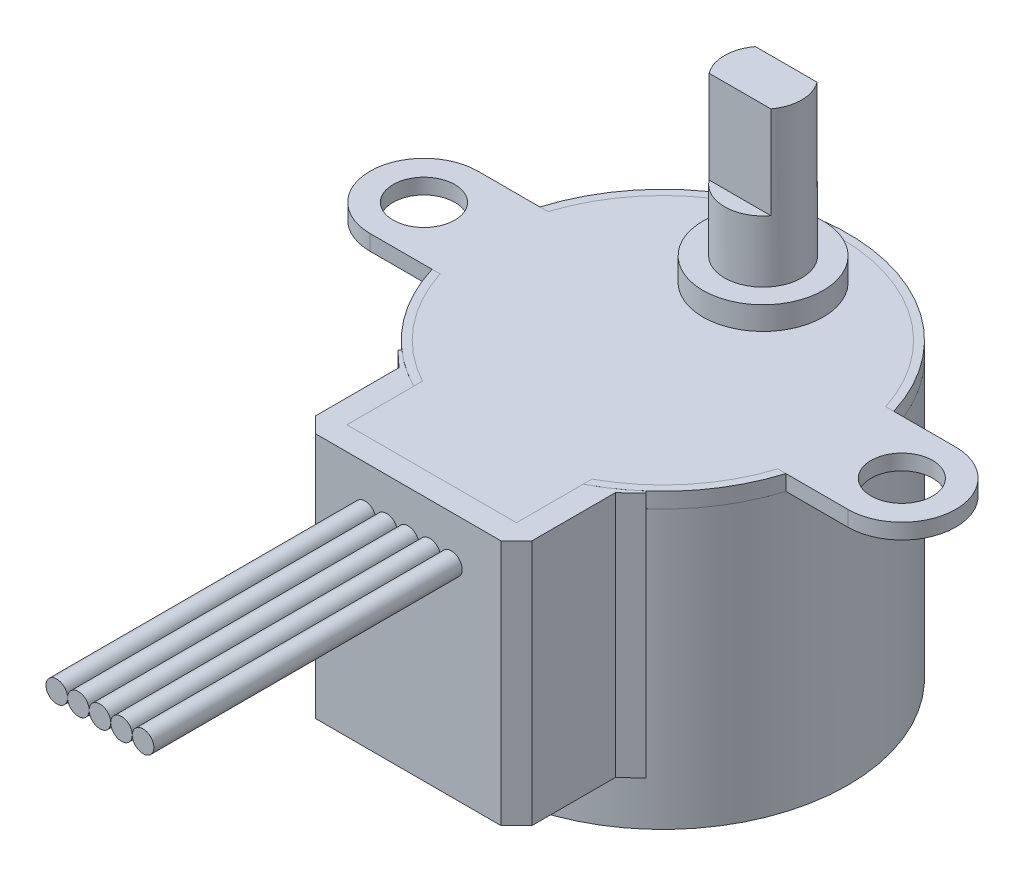
SolidWorks part; units mm, degrees
ref_plane "Front Plane" through (0, 0, 0) normal (0, 0, 1) x (1, 0, 0)
ref_plane "Top Plane" through (0, 0, 0) normal (0, 1, 0) x (1, 0, 0)
ref_plane "Right Plane" through (0, 0, 0) normal (1, 0, 0) x (0, 0, -1)
sketch "Sketch1" plane through (0, 0, 0) normal (0, 1, 0) x (1, 0, 0)
  circle A0 centre (0, 0) radius 12
  dimension "D1" = 24
extrude "Boss-Extrude1" add sketch "Sketch1" along normal blind 18
sketch "Sketch2" plane through (0, 18, 0) normal (0, 1, 0) x (1, 0, 0)
  line L0 (0, 16.9887) -> (0, 11.5) construction
  line L1 (10.9545, 3.5) -> (15.5, 3.5)
  line L2 (15.5, -3.5) -> (10.9545, -3.5)
  line L3 (-15.5, -3.5) -> (-10.9545, -3.5)
  line L4 (-10.9545, 3.5) -> (-15.5, 3.5)
  line L5 (-5.5, -10.0995) -> (-5.5, -15)
  line L6 (-5.5, -15) -> (5.5, -15)
  line L7 (5.5, -10.0995) -> (5.5, -15)
  line L8 (0, -11.5) -> (0, -20.5487) construction
  arc A0 (10.9545, 3.5) -> (-10.9545, 3.5) centre (0, 0) ccw
  circle A1 centre (15.5, 0) radius 2
  arc A2 (15.5, -3.5) -> (15.5, 3.5) centre (15.5, 0) ccw
  arc A3 (-15.5, -3.5) -> (-15.5, 3.5) centre (-15.5, 0) cw
  circle A4 centre (-15.5, 0) radius 2
  arc A5 (-10.9545, -3.5) -> (-5.5, -10.0995) centre (0, 0) ccw
  arc A6 (5.5, -10.0995) -> (10.9545, -3.5) centre (0, 0) ccw
  point P20 (0, -15)
  dimension "D1" = 23
  dimension "D3" = 4
  dimension "D2" = 15.5
  dimension "D4" = 3.5
  dimension "D5" = 7
  dimension "D6" = 15
  dimension "D7" = 5.5
extrude "Boss-Extrude2" add sketch "Sketch2" along normal blind 1 separate body
sketch "Sketch3" plane through (0, 18, 0) normal (0, 1, 0) x (1, 0, 0)
  line L0 (-11.4782, 3.5) -> (-10.9545, 3.5)
  line L3 (11.4782, -3.5) -> (10.9545, -3.5)
  line L5 (10.9545, 3.5) -> (11.4782, 3.5)
  line L6 (-10.9545, -3.5) -> (-11.4782, -3.5)
  line L7 (-5.5, -10.0995) -> (-5.5, -10.6654)
  line L8 (-5.5, -10.0995) -> (-5.5, -15) construction
  line L9 (5.5, -10.0995) -> (5.5, -10.6654)
  line L10 (5.5, -15) -> (5.5, -10.0995) construction
  arc A0 (-10.9545, -3.5) -> (-5.5, -10.0995) centre (0, 0) ccw
  circle A1 centre (0, 0) radius 12
  arc A2 (-11.4782, -3.5) -> (-5.5, -10.6654) centre (0, 0) ccw
  arc A3 (10.9545, 3.5) -> (-10.9545, 3.5) centre (0, 0) ccw
  arc A4 (11.4782, 3.5) -> (-11.4782, 3.5) centre (0, 0) ccw
  arc A5 (5.5, -10.0995) -> (10.9545, -3.5) centre (0, 0) ccw
  arc A6 (5.5, -10.6654) -> (11.4782, -3.5) centre (0, 0) ccw
  dimension "D1" = 0
extrude "Boss-Extrude3" add sketch "Sketch3" along normal blind 1 separate body
sketch "Sketch4" plane through (0, 19, 0) normal (0, 1, 0) x (1, 0, 0)
  line L0 (5.5, -15) -> (5.5, -10.0995) construction
  line L1 (-5.5, -15) -> (5.5, -15) construction
  line L2 (-5.5, -10.0995) -> (-5.5, -15) construction
  line L3 (5.5, -15) -> (5.5, -10.6654)
  line L4 (-5.5, -15) -> (5.5, -15)
  line L5 (-5.5, -10.6654) -> (-5.5, -15)
  line L6 (-7.02, -10.0995) -> (-7.02, -15.52)
  line L7 (-6.02, -16.52) -> (6.02, -16.52)
  line L8 (7.02, -15.52) -> (7.02, -10.0995)
  line L9 (-7.02, -10.0995) -> (-8.0447, -9.145)
  line L10 (-8.0447, -9.145) -> (-7.9259, -9.01)
  line L11 (0, 0) -> (0, -6.5603) construction
  line L12 (8.0447, -9.145) -> (7.9259, -9.01)
  line L13 (7.02, -10.0995) -> (8.0447, -9.145)
  line L14 (-5.5, -10.0995) -> (-5.5, -15) construction
  line L15 (5.5, -15) -> (5.5, -10.0995) construction
  line L16 (-7.02, -10.0995) -> (-7.02, -16.52) construction
  line L17 (-7.02, -16.52) -> (7.02, -16.52) construction
  line L18 (-7.02, -15.52) -> (-6.02, -16.52)
  line L19 (7.02, -16.52) -> (7.02, -10.0995) construction
  line L20 (6.02, -16.52) -> (7.02, -15.52)
  arc A0 (-7.9259, -9.01) -> (-5.5, -10.6654) centre (0, 0) ccw
  arc A1 (5.5, -10.6654) -> (7.9259, -9.01) centre (0, 0) ccw
  dimension "D1" = 1.52
extrude "Boss-Extrude4" add sketch "Sketch4" against normal blind 16 separate body
sketch "Sketch5" plane through (0, 3, 0) normal (0, -1, 0) x (1, 0, 0)
  line L12 (-5.5, 10.6654) -> (-5.5, 15)
  line L13 (-5.5, 15) -> (5.5, 15)
  line L14 (5.5, 15) -> (5.5, 10.6654)
  line L15 (7.9259, 9.01) -> (8.0447, 9.145)
  line L16 (8.0447, 9.145) -> (7.02, 10.0995)
  line L17 (7.02, 10.0995) -> (7.02, 15.52)
  line L18 (7.02, 15.52) -> (6.02, 16.52)
  line L19 (6.02, 16.52) -> (-6.02, 16.52)
  line L20 (-6.02, 16.52) -> (-7.02, 15.52)
  line L21 (-7.02, 15.52) -> (-7.02, 10.0995)
  line L22 (-7.02, 10.0995) -> (-8.0447, 9.145)
  line L23 (-8.0447, 9.145) -> (-7.9259, 9.01)
  line L27 (7.9259, 9.01) -> (8.0447, 9.145)
  line L28 (8.0447, 9.145) -> (7.02, 10.0995)
  line L29 (7.02, 10.0995) -> (7.02, 15.52)
  line L30 (7.02, 15.52) -> (6.02, 16.52)
  line L31 (6.02, 16.52) -> (-6.02, 16.52)
  line L32 (-6.02, 16.52) -> (-7.02, 15.52)
  line L33 (-7.02, 15.52) -> (-7.02, 10.0995)
  line L34 (-7.02, 10.0995) -> (-8.0447, 9.145)
  line L35 (-8.0447, 9.145) -> (-7.9259, 9.01)
  arc A0 (7.9259, 9.01) -> (-7.9259, 9.01) centre (0, 0) ccw
  arc A2 (-5.5, 10.6654) -> (-7.9259, 9.01) centre (0, 0) ccw
  arc A3 (7.9259, 9.01) -> (5.5, 10.6654) centre (0, 0) ccw
  arc A4 (-5.5, 10.6654) -> (-7.9259, 9.01) centre (0, 0) ccw
  arc A5 (7.9259, 9.01) -> (5.5, 10.6654) centre (0, 0) ccw
  arc M15 (-7.9259, 9.01) -> (-5.5, 10.6654) centre (0, 0) cw
  line M16 (-5.5, 10.6654) -> (-5.5, 15)
  line M17 (-5.5, 15) -> (5.5, 15)
  line M18 (5.5, 15) -> (5.5, 10.6654)
  arc M19 (5.5, 10.6654) -> (7.9259, 9.01) centre (0, 0) cw
  line M20 (7.9259, 9.01) -> (8.0447, 9.145)
  line M21 (8.0447, 9.145) -> (7.02, 10.0995)
  line M22 (7.02, 10.0995) -> (7.02, 15.52)
  line M23 (7.02, 15.52) -> (6.02, 16.52)
  line M24 (6.02, 16.52) -> (-6.02, 16.52)
  line M25 (-6.02, 16.52) -> (-7.02, 15.52)
  line M26 (-7.02, 15.52) -> (-7.02, 10.0995)
  line M27 (-7.02, 10.0995) -> (-8.0447, 9.145)
  line M28 (-8.0447, 9.145) -> (-7.9259, 9.01)
  dimension "D1" = 0
extrude "Boss-Extrude5" add sketch "Sketch5" against normal blind 1 contours A0 M18 M17 M16 | M28 M15 M16 M17 M18 M19 M20 M21 M22 M23 M24 M25 M26 M27 region at (-6.8639, 3, 10.0588) region at (0, 3, 13.2601)
sketch "Sketch6" plane through (0, 19, 0) normal (0, 1, 0) x (1, 0, 0)
  circle A0 centre (0, 6.5) radius 3.9
  dimension "D2" = 7.8
  dimension "D1" = 6.5
extrude "Boss-Extrude6" add sketch "Sketch6" along normal blind 1.5 separate body
sketch "Sketch7" plane through (0, 20.5, 0) normal (0, 1, 0) x (1, 0, 0)
  circle A0 centre (0, 6.5) radius 2.5
  dimension "D1" = 5
extrude "Boss-Extrude7" add sketch "Sketch7" along normal blind 4 separate body
sketch "Sketch8" plane through (0, 24.5, 0) normal (0, 1, 0) x (1, 0, 0)
  line L0 (-2, 8) -> (2, 8)
  line L1 (-2, 5) -> (2, 5)
  arc A0 (2, 5) -> (2, 8) centre (0, 6.5) ccw
  circle A1 centre (0, 6.5) radius 2.5
  arc A2 (-2, 8) -> (-2, 5) centre (0, 6.5) ccw
  dimension "D2" = 1.5
  dimension "D3" = 1.5
  dimension "D1" = 0
extrude "Boss-Extrude8" add sketch "Sketch8" along normal blind 6
sketch "Sketch9" plane through (0, 0, 16.52) normal (0, 0, 1) x (1, 0, 0)
  line L0 (-6.02, 19) -> (6.02, 19) construction
  circle A0 centre (-2.8, 16.1282) radius 0.7
  point P12 (0, 19)
  dimension "D1" = 1.4
  dimension "D3" = 2.8
extrude "Boss-Extrude9" add sketch "Sketch9" along normal blind 20 separate body
pattern_linear "LPattern1" count 5 spacing 1.4 along (1, 0, 0) of bodies 112
sketch "Sketch10" plane through (0, 0, 0) normal (0, -1, 0) x (1, 0, 0)
  text T0 "Designed by Tahamir Hasan Supto" font "Century Gothic" height in points 5
  point P3 (9.1895, 0)
  point P4 (-9.1895, 0)
extrude "Cut-Extrude1" cut sketch "Sketch10" against normal blind 0.4
sketch "Sketch11" plane through (0, 0, 0) normal (0, -1, 0) x (1, 0, 0)
  text T0 "24BYJ-48" font "Century Gothic" height in points 10
extrude "Cut-Extrude2" cut sketch "Sketch11" against normal blind 0.4
